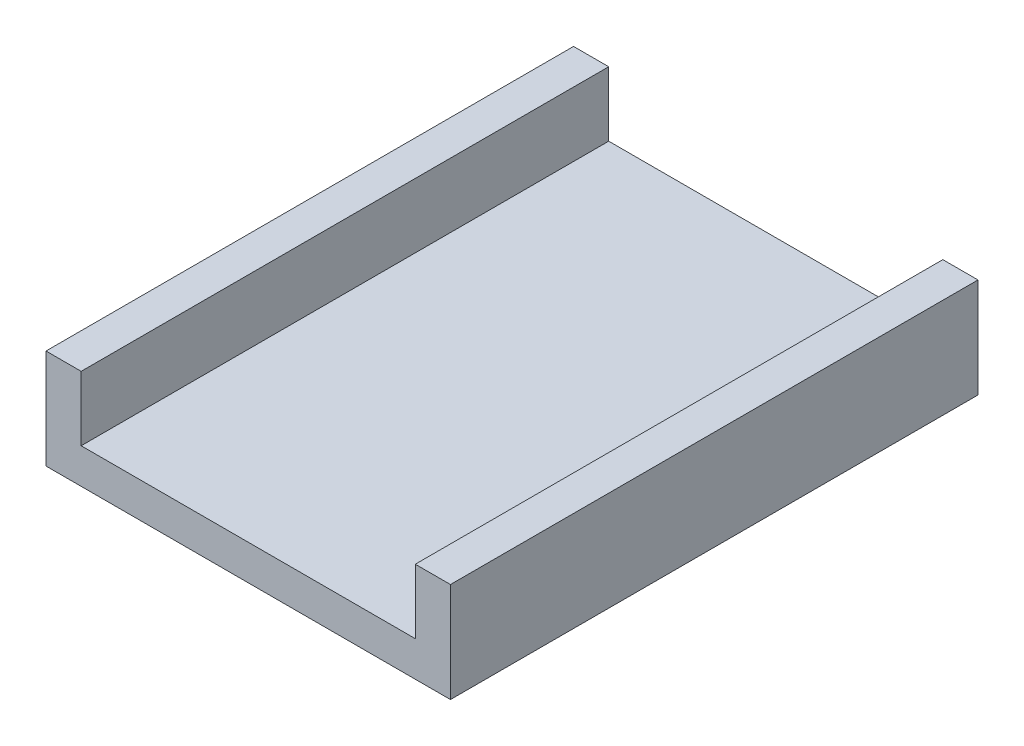
SolidWorks part; units mm, degrees
material "Custom Plastic"
ref_plane "Front Plane" through (0, 0, 0) normal (0, 0, 1) x (1, 0, 0)
ref_plane "Top Plane" through (0, 0, 0) normal (0, 1, 0) x (1, 0, 0)
ref_plane "Right Plane" through (0, 0, 0) normal (1, 0, 0) x (0, 0, -1)
sketch "Sketch2" plane through (0, 0, 0) normal (0, 1, 0) x (1, 0, 0)
  line L1 (-17.25, -22.5) -> (17.25, -22.5)
  line L2 (-17.25, -22.5) -> (-17.25, 22.5)
  line L3 (-17.25, 22.5) -> (17.25, 22.5)
  line L4 (17.25, -22.5) -> (17.25, 22.5)
  line L5 (-17.25, -22.5) -> (17.25, 22.5) construction
  line L6 (-17.25, 22.5) -> (17.25, -22.5) construction
  point P0 (0, 0)
  dimension "D1" = 34.5
  dimension "D2" = 45
extrude "Boss-Extrude1" add sketch "Sketch2" along normal blind 3
sketch "Sketch3" plane through (0, 3, 0) normal (0, 1, 0) x (1, 0, 0)
  line L0 (-14.25, 22.5) -> (-14.25, -22.5)
  line L1 (17.25, 22.5) -> (-17.25, 22.5) construction
  line L2 (-17.25, -22.5) -> (17.25, -22.5) construction
  line L3 (14.25, 22.5) -> (14.25, -22.5)
  line L4 (17.25, -22.5) -> (17.25, 22.5) construction
  line L5 (-17.25, 22.5) -> (-17.25, -22.5) construction
  line L6 (-14.25, 22.5) -> (-17.25, 22.5)
  line L7 (-17.25, 22.5) -> (-17.25, -22.5)
  line L8 (-17.25, -22.5) -> (-14.25, -22.5)
  line L9 (14.25, 22.5) -> (17.25, 22.5)
  line L10 (17.25, 22.5) -> (17.25, -22.5)
  line L11 (17.25, -22.5) -> (14.25, -22.5)
  dimension "D1" = 3
  dimension "D2" = 3
extrude "Boss-Extrude2" add sketch "Sketch3" along normal blind 5.5
sketch "Sketch4" plane through (0, 0, 0) normal (0, -1, 0) x (1, 0, 0)
  line L0 (-39.5265, 0) -> (35.5876, 0) construction
  line L2 (-39.5265, 13) -> (35.5876, 13) construction
  line L3 (-39.5265, -13) -> (42.0254, -13) construction
  line L4 (-11, 9.5) -> (11, 9.5)
  line L5 (-11, 9.5) -> (-11, 16.5)
  line L6 (-11, 16.5) -> (11, 16.5)
  line L7 (11, 9.5) -> (11, 16.5)
  line L8 (-11, 9.5) -> (11, 16.5) construction
  line L9 (-11, 16.5) -> (11, 9.5) construction
  line L10 (-11, -3.5) -> (11, -3.5)
  line L11 (-11, -3.5) -> (-11, 3.5)
  line L12 (-11, 3.5) -> (11, 3.5)
  line L13 (11, -3.5) -> (11, 3.5)
  line L14 (-11, -3.5) -> (11, 3.5) construction
  line L15 (-11, 3.5) -> (11, -3.5) construction
  line L16 (42.0254, -13) -> (0.6294, -13) construction
  line L17 (0, 29.2934) -> (0, -40.1208) construction
  line L19 (-11, -16.5) -> (11, -16.5)
  line L20 (-11, -16.5) -> (-11, -9.5)
  line L21 (-11, -9.5) -> (11, -9.5)
  line L22 (11, -16.5) -> (11, -9.5)
  line L23 (-11, -16.5) -> (11, -9.5) construction
  line L24 (-11, -9.5) -> (11, -16.5) construction
  point P3 (0, 13)
  point P4 (0, 13)
  point P11 (0, 0)
  point P21 (0, -13)
  point P22 (0, -13)
  dimension "D1" = 13
  dimension "D2" = 13
  dimension "D3" = 7
  dimension "D4" = 7
  dimension "D5" = 7
  dimension "D6" = 22
  dimension "D7" = 22
  dimension "D8" = 22
extrude "Cut-Extrude1" cut sketch "Sketch4" against normal blind 8
fillet "Fillet1" radius 3.5 12 edges at (-11, 1.5, -9.5) (-11, 1.5, -16.5) (11, 1.5, -9.5) (11, 1.5, -16.5) (11, 1.5, -3.5) (-11, 1.5, -3.5) (-11, 1.5, 3.5) (11, 1.5, 3.5) (11, 1.5, 9.5) (11, 1.5, 16.5) (-11, 1.5, 9.5) (-11, 1.5, 16.5)
sketch "Sketch5" plane through (0, 0, 0) normal (0, -1, 0) x (1, 0, 0)
  line L4 (17.25, -22.5) -> (17.25, 22.5)
  line L5 (17.25, 22.5) -> (-17.25, 22.5)
  line L6 (-17.25, 22.5) -> (-17.25, -22.5)
  line L7 (-17.25, -22.5) -> (17.25, -22.5)
  line L8 (17.25, -22.5) -> (17.25, 22.5)
  line L9 (17.25, 22.5) -> (-17.25, 22.5)
  line L10 (-17.25, 22.5) -> (-17.25, -22.5)
  line L11 (-17.25, -22.5) -> (17.25, -22.5)
  dimension "D1" = 0
extrude "Boss-Extrude3" add sketch "Sketch5" against normal up to surface (3 mm away) up to face at (0, 3, -13)
